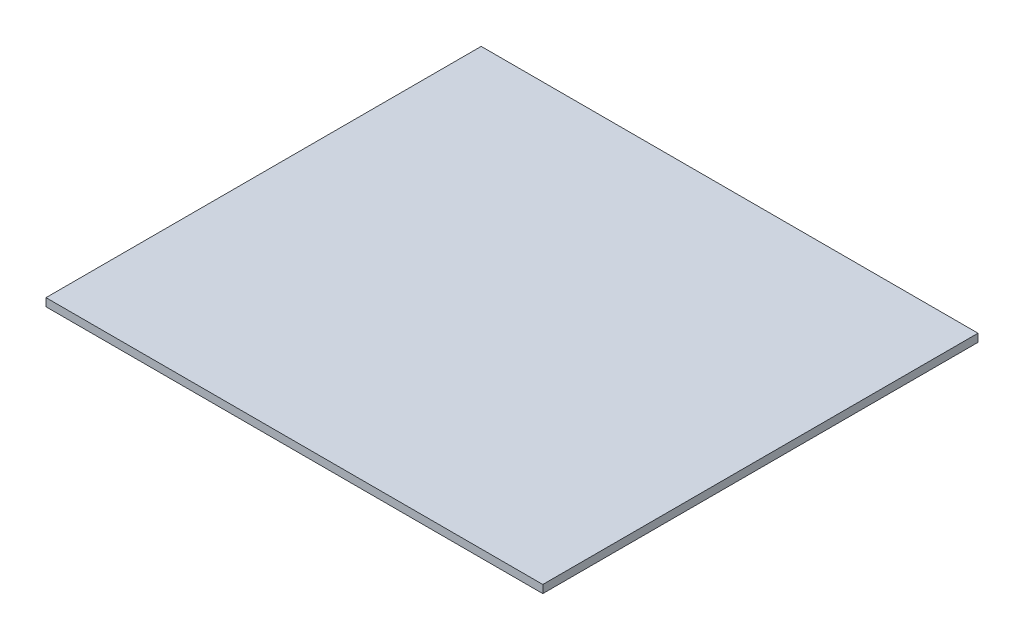
SolidWorks part; units mm, degrees
ref_plane "Front Plane" through (0, 0, 0) normal (0, 0, 1) x (1, 0, 0)
ref_plane "Top Plane" through (0, 0, 0) normal (0, 1, 0) x (1, 0, 0)
ref_plane "Right Plane" through (0, 0, 0) normal (1, 0, 0) x (0, 0, -1)
sketch "Sketch1" plane through (0, 0, 0) normal (0, 1, 0) x (1, 0, 0)
  line L1 (-125, -109.5) -> (125, -109.5)
  line L2 (-125, -109.5) -> (-125, 109.5)
  line L3 (-125, 109.5) -> (125, 109.5)
  line L4 (125, -109.5) -> (125, 109.5)
  line L5 (-125, -109.5) -> (125, 109.5) construction
  line L6 (-125, 109.5) -> (125, -109.5) construction
  point P0 (0, 0)
  dimension "D1" = 219
  dimension "D2" = 250
extrude "Boss-Extrude1" add sketch "Sketch1" along normal blind 4
